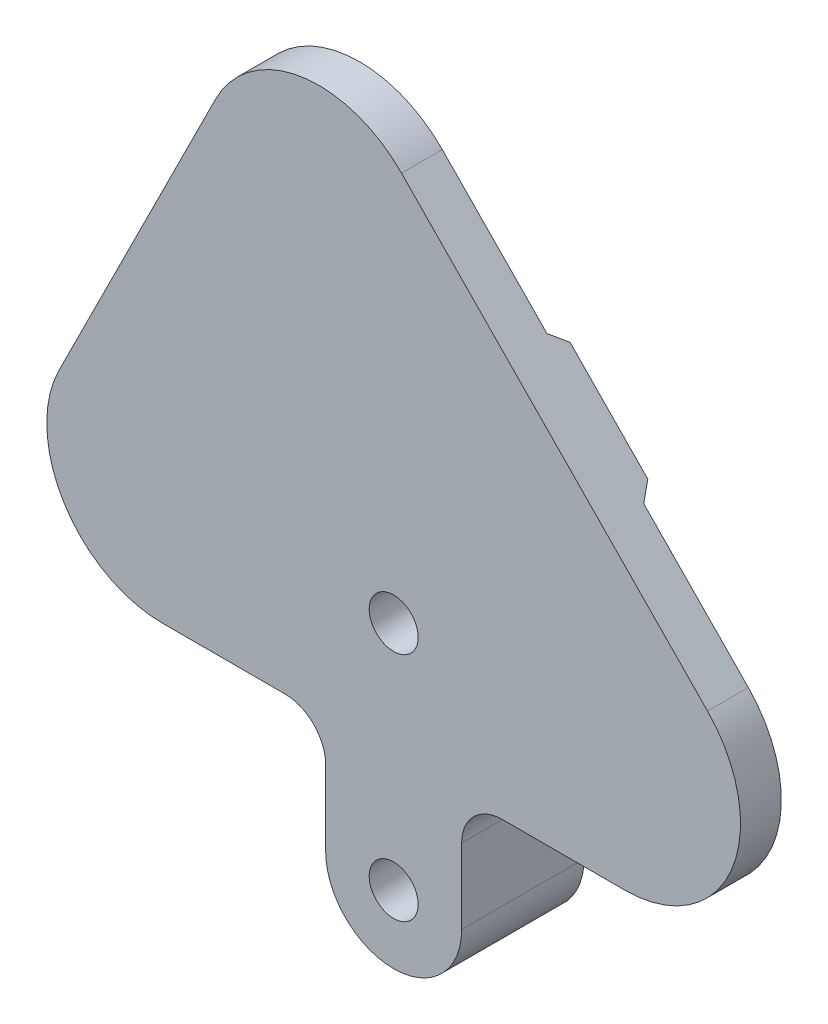
SolidWorks part; units mm, degrees
material "ABS"
ref_plane "Płaszczyzna przednia" through (0, 0, 0) normal (0, 0, 1) x (1, 0, 0)
ref_plane "Płaszczyzna górna" through (0, 0, 0) normal (0, 1, 0) x (1, 0, 0)
ref_plane "Płaszczyzna prawa" through (0, 0, 0) normal (1, 0, 0) x (0, 0, -1)
sketch "Szkic1" plane through (0, 0, 0) normal (0, 0, 1) x (1, 0, 0)
  line L0 (-7.6026, 3.8013) -> (3.8974, 26.8013)
  line L1 (17.5761, 28.944) -> (40.0761, 5.944)
  line L2 (34, -8.5) -> (25, -8.5)
  line L3 (22, -17) -> (22, -11.5)
  line L4 (12, -17) -> (12, -11.5)
  line L5 (9, -8.5) -> (0, -8.5)
  arc A0 (-7.6026, 3.8013) -> (0, -8.5) centre (0, 0) ccw
  arc A1 (17.5761, 28.944) -> (3.8974, 26.8013) centre (11.5, 23) ccw
  arc A2 (34, -8.5) -> (40.0761, 5.944) centre (34, 0) ccw
  circle A3 centre (17, 0) radius 1.8
  circle A4 centre (17, -17) radius 1.8
  arc A5 (12, -17) -> (22, -17) centre (17, -17) ccw
  arc A6 (12, -11.5) -> (9, -8.5) centre (9, -11.5) ccw
  arc A7 (22, -11.5) -> (25, -8.5) centre (25, -11.5) cw
  point P20 (12, -8.5)
  dimension "D1" = 17
  dimension "D2" = 17
  dimension "D3" = 3.6
  dimension "D4" = 34
  dimension "D5" = 17
  dimension "D6" = 23
  dimension "D7" = 17
  dimension "D8" = 11.5
  dimension "D10" = 23
  dimension "D11" = 17
  dimension "D12" = 3.6
  dimension "D14" = 5
  dimension "D15" = 3
  dimension "D9" = 23
  dimension "D13" = 17
extrude "Dodanie-wyciągnięcie1" add sketch "Szkic1" along normal blind 3
sketch "Szkic2" plane through (0, 0, 0) normal (0, 0, -1) x (-1, 0, 0)
  circle A0 centre (-34, 0) radius 6
  circle A1 centre (-11.5, 23) radius 6
  circle A2 centre (0, 0) radius 6
  dimension "D1" = 12
  dimension "D2" = 12
  dimension "D3" = 12
extrude "Wytnij-wyciągnięcie1" cut sketch "Szkic2" against normal blind 2
chamfer "Sfazowanie1" distance 0.5 angle 45 3 edges at (5.5, 23, 2) (-6, 0, 2) (28, 0, 2)
sketch "Szkic3" plane through (0, 0, 0) normal (0, 0, -1) x (-1, 0, 0)
  line L2 (-22, -17) -> (-22, 3.786)
  line L3 (-22.9021, 5.9305) -> (-31.6846, 14.522)
  line L4 (-25.9676, 20.366) -> (-16.0643, 10.678)
  line L5 (-40.0761, 5.944) -> (-17.5761, 28.944) construction
  line L6 (1.022, 16.9626) -> (-12.6248, 10.1392)
  line L7 (-3.8974, 26.8013) -> (7.6026, 3.8013) construction
  line L8 (2.6833, 13.64) -> (-10.3416, 7.1276)
  line L9 (-12, -17) -> (-12, 4.4443)
  line L10 (1.022, 16.9626) -> (2.6833, 13.64)
  line L11 (-25.9676, 20.366) -> (-31.6846, 14.522)
  arc A0 (-22, -17) -> (-12, -17) centre (-17, -17) ccw
  circle A2 centre (-17, 0) radius 1.8
  circle A3 centre (-17, -17) radius 1.8
  circle A4 centre (-34, 0) radius 5.5 construction
  circle A5 centre (-11.5, 23) radius 5.5 construction
  circle A6 centre (0, 0) radius 5.5 construction
  arc A7 (-10.3416, 7.1276) -> (-12, 4.4443) centre (-9, 4.4443) ccw
  arc A8 (-12.6248, 10.1392) -> (-16.0643, 10.678) centre (-13.9665, 12.8225) cw
  arc A9 (-22, 3.786) -> (-22.9021, 5.9305) centre (-25, 3.786) ccw
  dimension "D1" = 10
  dimension "D3" = 12
  dimension "D2" = 12
  dimension "D4" = 11
  dimension "D9" = 3
  dimension "D5" = 11
  dimension "D6" = 90
  dimension "D7" = 90
  dimension "D8" = 90
extrude "Dodanie-wyciągnięcie2" add sketch "Szkic3" along normal blind 1
chamfer "Sfazowanie2" distance 1 angle 45 9 edges at (12, -3.5279, 0) (22, -3.857, 0) (27.2933, 10.2262, 0) (22.2347, 4.9492, 0) (5.8014, 13.5509, 0) (14.4307, 9.8586, 0) (21.016, 15.522, 0) (3.8292, 10.3838, 0) (11.552, 6.0215, 0)
sketch "Szkic4" plane through (0, 0, -1) normal (0, 0, -1) x (-1, 0, 0)
  line L0 (-22, -12.1) -> (-12, -12.1)
  line L1 (-22, -12.1) -> (-22, -17)
  line L3 (-12, -12.1) -> (-12, -17)
  arc A0 (-22, -17) -> (-12, -17) centre (-17, -17) ccw
  circle A1 centre (-17, -17) radius 1.8
  dimension "D1" = 10
  dimension "D2" = 4.9
  dimension "D3" = 10
extrude "Dodanie-wyciągnięcie3" add sketch "Szkic4" along normal blind 5
